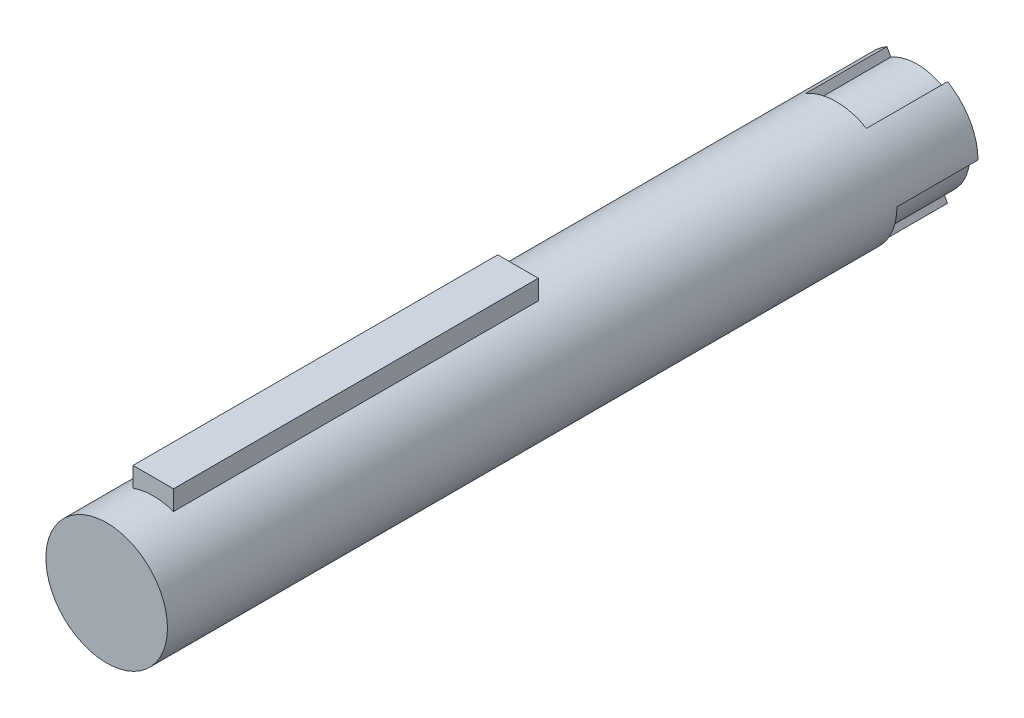
SolidWorks part; units mm, degrees
note: The reader was unsure of these and kept them because the rebuilt part matched: shared geometry of "Esboço3<5>".
ref_plane "Plano frontal" through (0, 0, 0) normal (0, 0, 1) x (1, 0, 0)
ref_plane "Plano superior" through (0, 0, 0) normal (0, 1, 0) x (1, 0, 0)
ref_plane "Plano direito" through (0, 0, 0) normal (1, 0, 0) x (0, 0, -1)
sketch "Esboço1" plane through (0, 0, 0) normal (0, 0, 1) x (1, 0, 0)
  circle A0 centre (0, 0) radius 7.5
  dimension "D1" = 15
extrude "Ressalto-extrusão1" add sketch "Esboço1" against normal blind 100
sketch "Esboço2" plane through (0, 0, 0) normal (0, 1, 0) x (1, 0, 0)
  line L5 (-7.5, 0) -> (7.5, 0) construction
  line L6 (-2.5, 5.75) -> (2.5, 5.75)
  line L8 (-2.5, 5.75) -> (-2.5, 50.75)
  line L10 (-2.5, 50.75) -> (2.5, 50.75)
  line L11 (2.5, 5.75) -> (2.5, 50.75)
  line L12 (-2.5, 5.75) -> (2.5, 50.75) construction
  line L13 (-2.5, 50.75) -> (2.5, 5.75) construction
  point P0 (0.2191, 28.25)
  point P1 (0, 28.25)
  point P8 (0, 0)
  dimension "D1" = 5.75
  dimension "D2" = 45
  dimension "D3" = 5
extrude "Ressalto-extrusão2" add sketch "Esboço2" along normal blind 9.5
sketch "Esboço3" plane through (0, 0, -100) normal (0, 0, -1) x (-1, 0, 0)
  line L0 (-3.7417, 6.5) -> (0, 0)
  line L1 (0, 0) -> (3.7417, 6.5)
  line L2 (0, 0) -> (-7.5, 0)
  line L3 (0, 0) -> (-3.7417, -6.5)
  line L4 (0, 0) -> (4.7048, -5.8408)
  line L5 (0, 0) -> (7.5, 0)
  circle A1 centre (0, 0) radius 7.5 construction
  circle A2 centre (0, 0) radius 6.5
  circle A4 centre (0, 0) radius 6.5
  dimension "D1" = 1
extrude "Corte-extrusão2" cut sketch "Esboço3" against normal blind 10 contours A4 L1 L0
extrude "Corte-extrusão3" cut sketch "Esboço3<5>" against normal blind 10 contours A4 L4 L0 L5 | A4 L2 L0 L3
sketch "Esboço3<5>" plane through (0, 0, -100) normal (0, 0, -1) x (-1, 0, 0) same geometry as "Esboço3"
